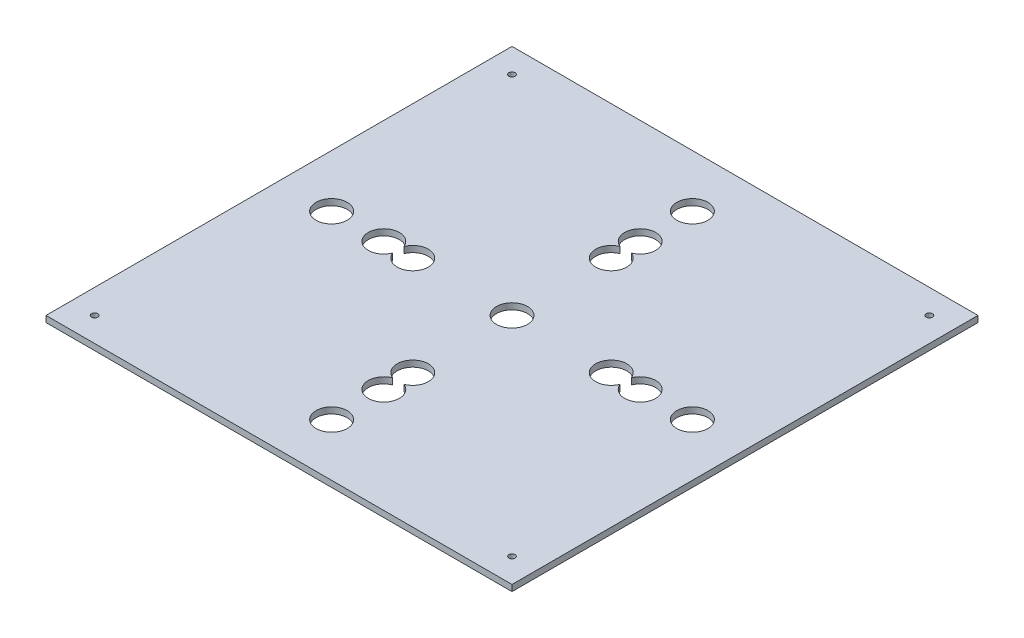
SolidWorks part; units mm, degrees
ref_plane "Front Plane" through (0, 0, 0) normal (0, 0, 1) x (1, 0, 0)
ref_plane "Top Plane" through (0, 0, 0) normal (0, 1, 0) x (1, 0, 0)
ref_plane "Right Plane" through (0, 0, 0) normal (1, 0, 0) x (0, 0, -1)
sketch "Sketch1" plane through (0, 0, 0) normal (0, 1, 0) x (1, 0, 0)
  line L0 (99.3613, 29.3962) -> (99.3613, 329.3962) construction
  line L1 (-50.6387, 329.3962) -> (249.3613, 329.3962)
  line L2 (-50.6387, 329.3962) -> (-50.6387, 29.3962)
  line L3 (-50.6387, 29.3962) -> (249.3613, 29.3962)
  line L4 (249.3613, 329.3962) -> (249.3613, 29.3962)
  line L5 (249.3613, 179.3962) -> (-50.6387, 179.3962) construction
  line L6 (-50.6387, 89.3962) -> (249.3613, 89.3962) construction
  line L7 (53.9399, 329.3962) -> (53.9399, 29.3962) construction
  line L8 (293.9399, 224.8175) -> (-6.0601, 224.8175) construction
  line L9 (189.3613, -15.1825) -> (189.3613, 284.8175) construction
  line L10 (249.3613, 329.3962) -> (-50.6387, 29.3962) construction
  line L11 (-50.6387, 329.3962) -> (249.3613, 29.3962) construction
  line L12 (-23.1637, 272.6462) -> (221.8863, 272.6462) construction
  line L13 (-23.1637, 272.6462) -> (-23.1637, 188.8962) construction
  line L14 (221.8863, 272.6462) -> (221.8863, 86.1462) construction
  line L15 (-23.1637, 86.1462) -> (221.8863, 86.1462) construction
  line L16 (-23.1637, 272.6462) -> (221.8863, 86.1462) construction
  line L17 (221.8863, 272.6462) -> (-23.1637, 86.1462) construction
  line L18 (-33.1637, 185.6462) -> (-33.1637, 188.8962) construction
  line L19 (-23.1637, 169.8962) -> (-33.1637, 169.8962) construction
  line L21 (-23.1637, 188.8962) -> (-33.1637, 188.8962) construction
  line L22 (-33.1637, 169.8962) -> (-33.1637, 173.1462) construction
  line L23 (-33.1637, 185.6462) -> (-50.6387, 185.6462) construction
  line L25 (-33.1637, 173.1462) -> (-50.6387, 173.1462) construction
  line L26 (-50.6387, 185.6462) -> (-50.6387, 173.1462) construction
  line L27 (-33.1637, 185.6462) -> (-50.6387, 173.1462) construction
  line L28 (-33.1637, 173.1462) -> (-50.6387, 185.6462) construction
  line L29 (-23.1637, 169.8962) -> (-23.1637, 86.1462) construction
  circle A0 centre (-16.7587, 179.3962) radius 10.02
  arc A1 (26.1613, 183.0207) -> (26.1613, 175.7716) centre (16.8413, 179.3962) ccw
  circle A2 centre (99.3613, 179.3962) radius 10
  circle A3 centre (-34.989, 313.7464) radius 2
  circle A4 centre (233.7116, 313.7464) radius 2
  circle A5 centre (233.7116, 45.0459) radius 2
  circle A6 centre (-34.989, 45.0459) radius 2
  arc A7 (26.1613, 175.7716) -> (26.1613, 183.0207) centre (35.4813, 179.3962) ccw
  circle A8 centre (99.3613, 295.5162) radius 10.02
  arc A9 (102.9859, 252.5962) -> (95.7367, 252.5962) centre (99.3613, 261.9162) ccw
  arc A10 (95.7367, 252.5962) -> (102.9859, 252.5962) centre (99.3613, 243.2762) ccw
  circle A11 centre (215.4813, 179.3962) radius 10.02
  arc A12 (172.5613, 175.7716) -> (172.5613, 183.0207) centre (181.8813, 179.3962) ccw
  arc A13 (172.5613, 183.0207) -> (172.5613, 175.7716) centre (163.2413, 179.3962) ccw
  circle A14 centre (99.3613, 63.2762) radius 10.02
  arc A15 (95.7367, 106.1962) -> (102.9859, 106.1962) centre (99.3613, 96.8762) ccw
  arc A16 (102.9859, 106.1962) -> (95.7367, 106.1962) centre (99.3613, 115.5162) ccw
  point P10 (99.3613, 89.3962)
  point P11 (189.3613, 134.8175)
  point P12 (53.9399, 179.3962)
  point P19 (121.6506, 157.1068)
  point P23 (99.3613, 179.3962)
  point P28 (99.3613, 179.3962)
  point P31 (-23.1637, 179.3962)
  point P39 (99.3613, 179.3962)
  point P60 (99.3613, 179.3962)
  point P72 (-41.9012, 179.3962)
  point P73 (0, 0)
  dimension "D5" = 116.12
  dimension "D6" = 82.52
  dimension "D7" = 190
  dimension "D9" = 63.88
  dimension "D1" = 90
  dimension "D3" = 300
  dimension "D4" = 300
  dimension "D11" = 186.5
  dimension "D12" = 245.05
  dimension "D2" = 4
  dimension "D8" = 4
  dimension "D10" = 4
extrude "Boss-Extrude1" add sketch "Sketch1" along normal blind 4
